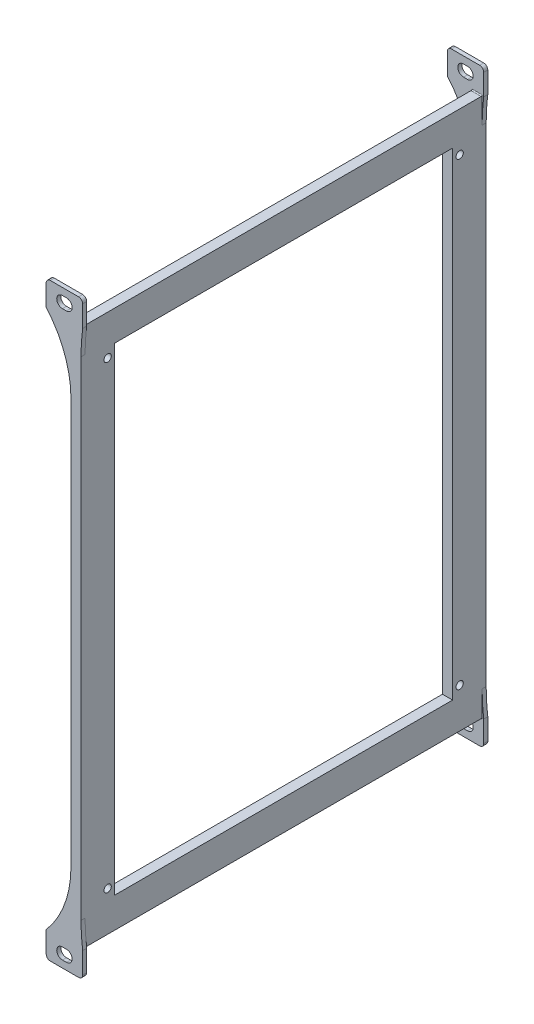
SolidWorks part; units mm, degrees
ref_plane "Front Plane" through (0, 0, 0) normal (1, 0, 0) x (0, 1, 0)
ref_plane "Top Plane" through (0, 0, 0) normal (0, 0, 1) x (0, 1, 0)
ref_plane "Right Plane" through (0, 0, 0) normal (0, 1, 0) x (-1, 0, 0)
sketch "Sketch1" plane through (0, 0, 0) normal (1, 0, 0) x (0, 1, 0)
  line L0 (-133, 83.395) -> (-133, -83.395)
  line L1 (-113.375, -86.895) -> (113.375, -86.895) construction
  line L2 (-113.375, -86.895) -> (-113.375, 86.895) construction
  line L3 (-113.375, 86.895) -> (113.375, 86.895) construction
  line L4 (113.375, -86.895) -> (113.375, 86.895) construction
  line L5 (-113.375, -86.895) -> (113.375, 86.895) construction
  line L6 (-113.375, 86.895) -> (113.375, -86.895) construction
  line L7 (-133, 83.395) -> (133, 83.395)
  line L8 (-133, 83.395) -> (-133, 90.395)
  line L9 (-133, 90.395) -> (133, 90.395)
  line L10 (133, 83.395) -> (133, 90.395)
  line L11 (-133, 83.395) -> (133, 90.395) construction
  line L12 (-133, 90.395) -> (133, 83.395) construction
  line L13 (-133, -90.395) -> (133, -90.395)
  line L14 (-133, -90.395) -> (-133, -83.395)
  line L15 (-133, -83.395) -> (133, -83.395)
  line L16 (133, -90.395) -> (133, -83.395)
  line L17 (-133, -90.395) -> (133, -83.395) construction
  line L18 (-133, -83.395) -> (133, -90.395) construction
  line L20 (-133, 83.395) -> (-118, 83.395)
  line L21 (-133, 83.395) -> (-133, -83.395)
  line L22 (-133, -83.395) -> (-118, -83.395)
  line L23 (-118, 83.395) -> (-118, -83.395)
  line L24 (-133, 83.395) -> (-118, -83.395) construction
  line L25 (-133, -83.395) -> (-118, 83.395) construction
  line L26 (133, 83.395) -> (118, 83.395)
  line L27 (133, 83.395) -> (133, -83.395)
  line L28 (133, -83.395) -> (118, -83.395)
  line L29 (118, 83.395) -> (118, -83.395)
  line L30 (133, 83.395) -> (118, -83.395) construction
  line L31 (133, -83.395) -> (118, 83.395) construction
  circle A0 centre (-113.375, 86.895) radius 1.8
  circle A1 centre (113.375, 86.895) radius 1.8
  circle A2 centre (113.375, -86.895) radius 1.8
  circle A3 centre (-113.375, -86.895) radius 1.8
  point P0 (0, 0)
  point P10 (0, 86.895)
  point P15 (0, -86.895)
  point P20 (148.3209, -90.395)
  point P23 (-125.5, 0)
  point P26 (125.5, 0)
  dimension "D3" = 3.6
  dimension "D1" = 226.75
  dimension "D2" = 173.79
  dimension "D4" = 7
  dimension "D5" = 7
  dimension "D6" = 15
  dimension "D7" = 15
  dimension "D8" = 236
extrude "Boss-Extrude1" add sketch "Sketch1" along normal blind 5 contours L7 L10 L9 L8 A1 A0 | L7 L29 L15 L27 | L23 L7 L0 L15 | L13 L16 L15 L14 A3 A2
sketch "Sketch2" plane through (5, 0, 0) normal (1, 0, 0) x (0, 1, 0)
  line L0 (-133, 90.395) -> (133, 90.395) construction
  line L1 (-133, 90.395) -> (133, 90.395)
  line L2 (-133, 90.395) -> (-133, 100)
  line L3 (-133, 100) -> (133, 100)
  line L4 (133, 90.395) -> (133, 100)
  line L5 (-133, 90.395) -> (133, 100) construction
  line L6 (-133, 100) -> (133, 90.395) construction
  line L7 (-133, -90.395) -> (133, -90.395) construction
  line L8 (-133, -90.395) -> (133, -90.395)
  line L9 (-133, -90.395) -> (-133, -100)
  line L10 (-133, -100) -> (133, -100)
  line L11 (133, -90.395) -> (133, -100)
  line L12 (-133, -90.395) -> (133, -100) construction
  line L13 (-133, -100) -> (133, -90.395) construction
  point P4 (0, 95.1975)
  point P6 (133, -90.395)
  point P13 (0, -95.1975)
  point P17 (129.6253, -90.395)
  point P18 (0, 0)
  point P21 (0, 0)
  line M9 (-133, -90.395) -> (133, -90.395)
  line M11 (133, 90.395) -> (-133, 90.395)
  dimension "D1" = 200
extrude "Boss-Extrude2" add sketch "Sketch2" against normal up to surface (5 mm away) contours L4 L3 L2 M11 | L11 L9 L10 M9 up to face at (0, 0, 0)
sketch "Sketch3" plane through (0, 0, -100) normal (0, 0, -1) x (1, 0, 0)
  line L0 (0, 133) -> (5, 133) construction
  line L1 (-12.215, 133) -> (5.785, 133)
  line L2 (-12.215, 133) -> (-12.215, 145.5)
  line L3 (-12.215, 145.5) -> (5.785, 145.5)
  line L4 (5.785, 133) -> (5.785, 145.5)
  line L5 (-12.215, 133) -> (5.785, 145.5) construction
  line L6 (-12.215, 145.5) -> (5.785, 133) construction
  line L8 (-4.215, 139.25) -> (-2.215, 139.25) construction
  line L9 (-4.215, 142.05) -> (-2.215, 142.05)
  line L10 (-4.215, 136.45) -> (-2.215, 136.45)
  line L11 (5.785, 145.5) -> (5, 145.5)
  line L12 (5.785, 145.5) -> (5.785, 133)
  line L13 (5.785, 133) -> (5, 133)
  line L14 (5, 145.5) -> (5, 133)
  line L15 (5.785, 145.5) -> (5, 133) construction
  line L16 (5.785, 133) -> (5, 145.5) construction
  arc A0 (-4.215, 142.05) -> (-4.215, 136.45) centre (-4.215, 139.25) ccw
  arc A1 (-2.215, 136.45) -> (-2.215, 142.05) centre (-2.215, 139.25) ccw
  point P4 (-3.215, 139.25)
  point P8 (2.5, 133)
  point P11 (-3.215, 139.25)
  point P19 (5.3925, 139.25)
  line M14 (5, 133) -> (0, 133)
  dimension "D1" = 12.5
  dimension "D2" = 18
  dimension "D3" = 2
  dimension "D4" = 5.6
  dimension "D5" = 5.715
extrude "Boss-Extrude3" add sketch "Sketch3" against normal blind 2 contours L4 L3 L2 L1 A1 L10 A0 L9 M14 | L14 L11 L4 M14
fillet "Fillet1" radius 0.5 1 edges at (2.5, -133, -98)
fillet "Fillet2" radius 50 1 edges at (0, -133, -99)
fillet "Fillet3" radius 2 2 edges at (-12.215, -145.5, -99) (5.785, -145.5, -99)
mirror "Mirror1" about plane through (0, 0, 0) normal (0, 0, 1) of bodies 103 104
mirror "Mirror2" about plane through (0, 0, 0) normal (0, 1, 0) of bodies 105
fillet "Fillet4" radius 100 4 edges at (5, 133, 99) (5, 133, -99) (5, -133, -99) (5, -133, 99)
